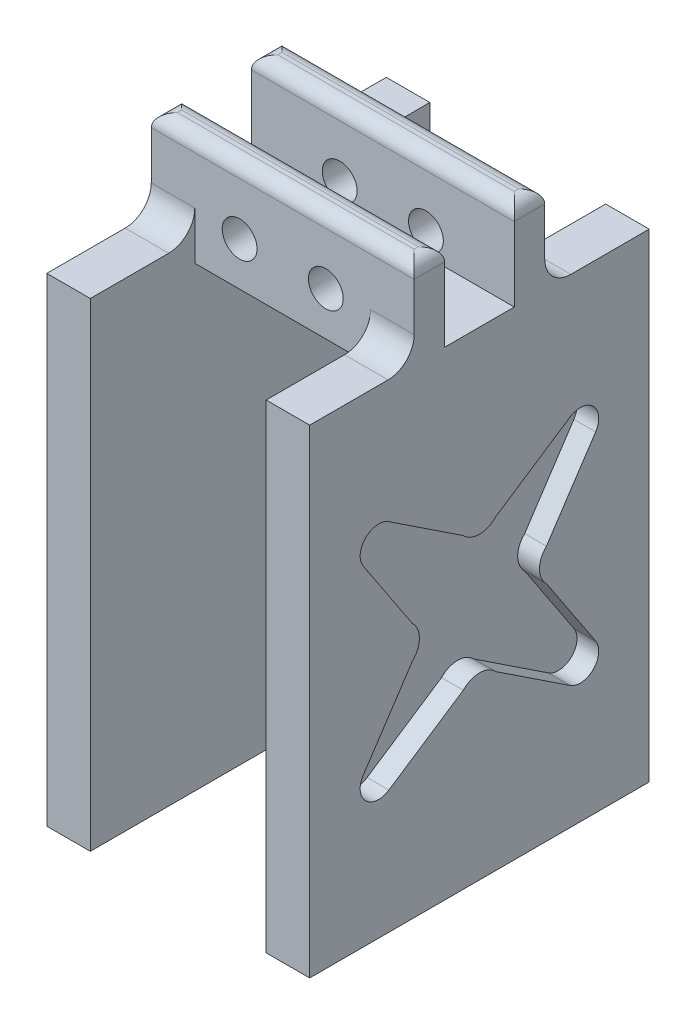
SolidWorks part; units mm, degrees
ref_plane "Front Plane" through (0, 0, 0) normal (0, 0, 1) x (1, 0, 0)
ref_plane "Top Plane" through (0, 0, 0) normal (0, 1, 0) x (1, 0, 0)
ref_plane "Right Plane" through (0, 0, 0) normal (1, 0, 0) x (0, 0, -1)
sketch "Sketch1" plane through (0, 0, 0) normal (1, 0, 0) x (0, 0, -1)
  line L0 (0, 27.5) -> (-4, 32.5) construction
  line L1 (-19.5, -27.5) -> (19.5, -27.5)
  line L2 (-19.5, -27.5) -> (-19.5, 27.5)
  line L3 (-19.5, 27.5) -> (-7.5, 27.5)
  line L4 (19.5, -27.5) -> (19.5, 27.5)
  line L5 (-19.5, -27.5) -> (19.5, 27.5) construction
  line L6 (-19.5, 27.5) -> (19.5, -27.5) construction
  line L8 (4, 27.5) -> (4, 37.5)
  line L9 (4, 37.5) -> (7.5, 37.5)
  line L10 (7.5, 27.5) -> (7.5, 37.5)
  line L12 (-4, 27.5) -> (-4, 37.5)
  line L13 (-4, 37.5) -> (-7.5, 37.5)
  line L14 (-7.5, 27.5) -> (-7.5, 37.5)
  line L15 (0, 27.5) -> (4, 32.5) construction
  line L16 (7.5, 27.5) -> (19.5, 27.5)
  line L17 (-4, 27.5) -> (4, 27.5)
  point P0 (0, 0)
  dimension "D1" = 55
  dimension "D2" = 39
  dimension "D3" = 8
  dimension "D4" = 10
  dimension "D5" = 3.5
extrude "Boss-Extrude1" add sketch "Sketch1" along normal mid plane 30.2
sketch "Sketch2" plane through (0, 0, 19.5) normal (0, 0, 1) x (1, 0, 0)
  line L0 (15.1, -27.5) -> (-15.1, -27.5) construction
  line L1 (-10.1, -27.5) -> (10.1, -27.5)
  line L2 (-10.1, -27.5) -> (-10.1, 25)
  line L3 (-10.1, 25) -> (10.1, 25)
  line L4 (10.1, -27.5) -> (10.1, 25)
  line L5 (-10.1, -1.25) -> (-15.1, -1.25) construction
  line L6 (-15.1, 27.5) -> (-15.1, -27.5) construction
  line L7 (10.1, -1.25) -> (15.1, -1.25) construction
  line L8 (15.1, 27.5) -> (15.1, -27.5) construction
  dimension "D1" = 52.5
  dimension "D2" = 20.2
extrude "Cut-Extrude1" cut sketch "Sketch2" against normal up to surface (39 mm away) up to face at (0, 0, -19.5)
sketch "Sketch3" plane through (0, 27.5, 0) normal (0, 1, 0) x (1, 0, 0)
  line L0 (15.1, -19.5) -> (-15.1, -19.5) construction
  line L1 (-10.1, -19.5) -> (10.1, -19.5)
  line L2 (-10.1, -19.5) -> (-10.1, -7.5)
  line L3 (-10.1, -7.5) -> (10.1, -7.5)
  line L4 (10.1, -19.5) -> (10.1, -7.5)
  line L5 (15.1, -7.5) -> (-15.1, -7.5) construction
  line L6 (15.1, 7.5) -> (-15.1, 7.5) construction
  line L7 (-10.1, 7.5) -> (10.1, 7.5)
  line L8 (-10.1, 7.5) -> (-10.1, 19.5)
  line L9 (-10.1, 19.5) -> (10.1, 19.5)
  line L10 (10.1, 7.5) -> (10.1, 19.5)
  line L11 (15.1, 19.5) -> (-15.1, 19.5) construction
  line L12 (-10.1, -13.5) -> (-15.1, -13.5) construction
  line L13 (-15.1, -7.5) -> (-15.1, -19.5) construction
  line L14 (10.1, 13.5) -> (15.1, 13.5) construction
  line L15 (15.1, 19.5) -> (15.1, 7.5) construction
  line L16 (10.1, -13.5) -> (15.1, -13.5) construction
  line L17 (15.1, -7.5) -> (15.1, -19.5) construction
  line L18 (-10.1, 13.5) -> (-15.1, 13.5) construction
  line L19 (-15.1, 19.5) -> (-15.1, 7.5) construction
  dimension "D1" = 5
  dimension "D2" = 5
extrude "Cut-Extrude2" cut sketch "Sketch3" against normal up to surface (2.5 mm away) up to face at (0, 25, 0)
fillet "Fillet1" radius 3 4 edges at (-12.6, 27.5, -7.5) (12.6, 27.5, -7.5) (-12.6, 27.5, 7.5) (12.6, 27.5, 7.5)
fillet "Fillet2" radius 1.5 8 edges at (0, 37.5, -7.5) (15.1, 37.5, -5.75) (0, 37.5, -4) (-15.1, 37.5, -5.75) (0, 37.5, 4) (15.1, 37.5, 5.75) (0, 37.5, 7.5) (-15.1, 37.5, 5.75)
sketch "Sketch4" plane through (0, 0, 7.5) normal (0, 0, 1) x (1, 0, 0)
  line L0 (0, 36) -> (0, 25) construction
  line L1 (15.1, 36) -> (-15.1, 36) construction
  line L2 (-10.1, 25) -> (10.1, 25) construction
  circle A0 centre (-4.95, 30) radius 2
  circle A2 centre (4.95, 30) radius 2
  dimension "D1" = 4
  dimension "D2" = 6
  dimension "D3" = 4.95
extrude "Cut-Extrude3" cut sketch "Sketch4" against normal up to surface (15 mm away) up to face at (0, 30.5, -7.5)
sketch "Sketch5" plane through (15.1, 0, 0) normal (1, 0, 0) x (0, 0, -1)
  line L0 (-13.0815, 13.0815) -> (13.0815, 13.0815) construction
  line L1 (0, 13.0815) -> (0, -13.0815) construction
  line L2 (13.0815, -13.0815) -> (-13.0815, -13.0815) construction
  line L3 (13.0815, 13.0815) -> (13.0815, -13.0815) construction
  line L4 (-7.6927, 1.859) -> (-1.859, 7.6927) construction
  line L5 (-13.0815, 13.0815) -> (13.0815, -13.0815) construction
  line L6 (-14.5654, 0) -> (13.0815, 0) construction
  line L7 (13.3508, 10.4058) -> (7.6927, 1.859)
  line L8 (10.4058, 13.3508) -> (1.859, 7.6927)
  line L9 (7.6927, 1.859) -> (1.859, 7.6927) construction
  line L10 (-13.3508, -10.4058) -> (-7.6927, -1.859)
  line L11 (-10.4058, -13.3508) -> (-1.859, -7.6927)
  line L12 (-10.4058, 13.3508) -> (-1.859, 7.6927)
  line L13 (-13.3508, 10.4058) -> (-7.6927, 1.859)
  line L14 (-13.0815, -13.0815) -> (13.0815, 13.0815) construction
  line L15 (10.4058, -13.3508) -> (1.859, -7.6927)
  line L16 (13.3508, -10.4058) -> (7.6927, -1.859)
  circle A0 centre (0, 0) radius 6.8943 construction
  arc A1 (-7.6927, 1.859) -> (-7.6927, -1.859) centre (-9.4579, 0) cw
  arc A2 (13.3508, -10.4058) -> (10.4058, -13.3508) centre (11.5789, -11.5789) cw
  arc A3 (-13.3508, 10.4058) -> (-10.4058, 13.3508) centre (-11.5789, 11.5789) cw
  arc A4 (13.3508, 10.4058) -> (10.4058, 13.3508) centre (11.5789, 11.5789) ccw
  arc A5 (7.6927, 1.859) -> (7.6927, -1.859) centre (9.4579, 0) ccw
  arc A6 (-13.3508, -10.4058) -> (-10.4058, -13.3508) centre (-11.5789, -11.5789) ccw
  arc A7 (1.859, -7.6927) -> (-1.859, -7.6927) centre (0, -9.4579) ccw
  arc A8 (1.859, 7.6927) -> (-1.859, 7.6927) centre (0, 9.4579) cw
  point P6 (13.0815, 0)
  point P7 (0, 13.0815)
  point P56 (0, 6.8943)
  point P57 (6.8943, 0)
  dimension "D4" = 9.75
  dimension "D5" = 2.125
  dimension "D1" = 37
  dimension "D2" = 8.25
  dimension "D3" = 90
  dimension "D6" = 10.25
extrude "Cut-Extrude4" cut sketch "Sketch5" against normal blind 2.5
sketch "Sketch6" plane through (-15.1, 0, 0) normal (-1, 0, 0) x (0, 0, 1)
  line L0 (-13.0815, 13.0815) -> (13.0815, 13.0815) construction
  line L1 (0, 13.0815) -> (0, -13.0815) construction
  line L2 (13.0815, -13.0815) -> (-13.0815, -13.0815) construction
  line L3 (13.0815, 13.0815) -> (13.0815, -13.0815) construction
  line L4 (-7.6927, 1.859) -> (-1.859, 7.6927) construction
  line L5 (-13.0815, 13.0815) -> (13.0815, -13.0815) construction
  line L6 (-9.0732, 0) -> (13.0815, 0) construction
  line L7 (13.3508, 10.4058) -> (7.6927, 1.859)
  line L8 (10.4058, 13.3508) -> (1.859, 7.6927)
  line L9 (7.6927, 1.859) -> (1.859, 7.6927) construction
  line L10 (-13.3508, -10.4058) -> (-7.6927, -1.859)
  line L11 (-10.4058, -13.3508) -> (-1.859, -7.6927)
  line L12 (-10.4058, 13.3508) -> (-1.859, 7.6927)
  line L13 (-13.3508, 10.4058) -> (-7.6927, 1.859)
  line L14 (-13.0815, -13.0815) -> (13.0815, 13.0815) construction
  line L15 (10.4058, -13.3508) -> (1.859, -7.6927)
  line L16 (13.3508, -10.4058) -> (7.6927, -1.859)
  circle A0 centre (0, 0) radius 6.8943 construction
  arc A1 (-7.6927, 1.859) -> (-7.6927, -1.859) centre (-9.4579, 0) cw
  arc A2 (13.3508, -10.4058) -> (10.4058, -13.3508) centre (11.5789, -11.5789) cw
  arc A3 (-13.3508, 10.4058) -> (-10.4058, 13.3508) centre (-11.5789, 11.5789) cw
  arc A4 (13.3508, 10.4058) -> (10.4058, 13.3508) centre (11.5789, 11.5789) ccw
  arc A5 (7.6927, 1.859) -> (7.6927, -1.859) centre (9.4579, 0) ccw
  arc A6 (-13.3508, -10.4058) -> (-10.4058, -13.3508) centre (-11.5789, -11.5789) ccw
  arc A7 (1.859, -7.6927) -> (-1.859, -7.6927) centre (0, -9.4579) ccw
  arc A8 (1.859, 7.6927) -> (-1.859, 7.6927) centre (0, 9.4579) cw
  point P6 (13.0815, 0)
  point P7 (0, 13.0815)
  point P36 (0, 6.8943)
  point P37 (6.8943, 0)
  dimension "D5" = 2.125
  dimension "D1" = 8.25
  dimension "D2" = 90
  dimension "D3" = 37
  dimension "D4" = 9.75
  dimension "D6" = 10.25
extrude "Cut-Extrude5" cut sketch "Sketch6" against normal blind 2.5
